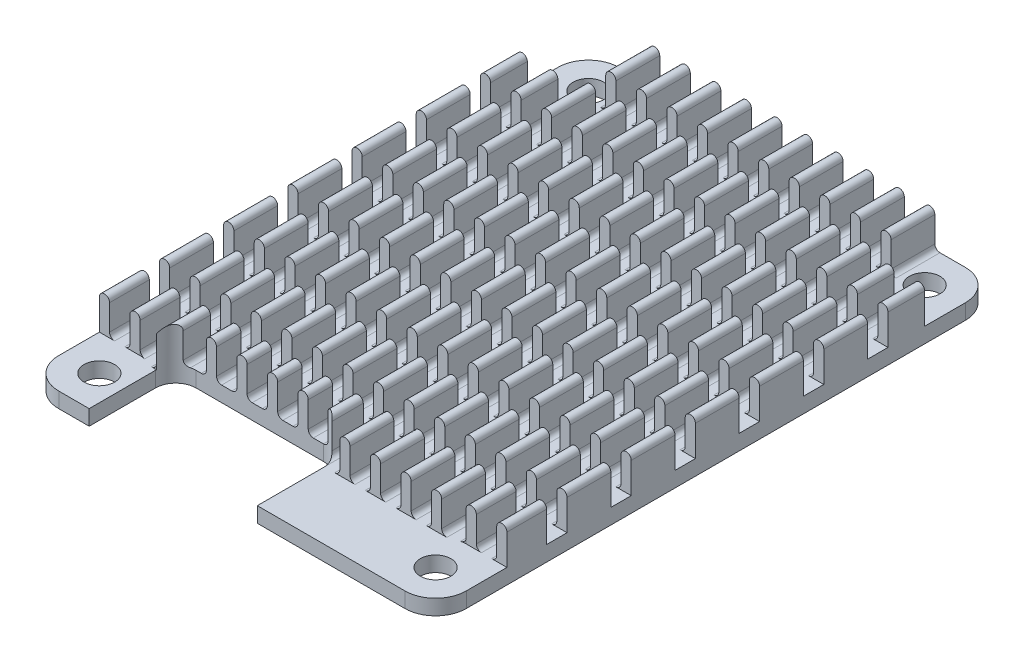
SolidWorks part; units mm, degrees
ref_plane "Ebene vorne" through (0, 0, 0) normal (0, 0, 1) x (1, 0, 0)
ref_plane "Ebene oben" through (0, 0, 0) normal (0, 1, 0) x (1, 0, 0)
ref_plane "Ebene rechts" through (0, 0, 0) normal (1, 0, 0) x (0, 0, -1)
sketch "Skizze1" plane through (0, 0, 0) normal (0, 1, 0) x (1, 0, 0)
  line L0 (20, -24.4903) -> (20, 24.4969)
  line L1 (17, 27.4969) -> (-17, 27.4969)
  line L2 (-20, 24.4969) -> (-20, -24.5035)
  line L3 (2.5, -27.5031) -> (17, -27.5031)
  line L4 (-20, -19.0031) -> (-20, -24.5035)
  line L5 (-16.9542, -27.5031) -> (-14, -27.5031)
  line L6 (-14, -27.5031) -> (-14, -21.0031)
  line L7 (-12.0085, -19.0031) -> (0.5, -19.0031)
  line L8 (2.5, -21.0077) -> (2.5, -27.5031)
  line L9 (2.5, -27.5031) -> (17, -27.5031)
  line L10 (20, -24.4903) -> (20, -19.0031)
  line L11 (-14, -27.5031) -> (-16.9542, -27.5031)
  line L13 (-25.9616, 32.7845) -> (24.6892, 32.7845)
  line L14 (-25.9616, 32.7845) -> (-25.9616, -32.0927)
  line L15 (-25.9616, -32.0927) -> (24.6892, -32.0927)
  line L16 (24.6892, 32.7845) -> (24.6892, -32.0927)
  circle A0 centre (-16.5, 23.9969) radius 1.5
  circle A1 centre (16.5, 23.9969) radius 1.5
  circle A2 centre (16.5, -24.0031) radius 1.5
  circle A3 centre (-16.5, -24.0031) radius 1.5
  arc A4 (20, 24.4969) -> (17, 27.4969) centre (17, 24.4969) ccw
  arc A5 (-17, 27.4969) -> (-20, 24.4969) centre (-17, 24.4969) ccw
  arc A6 (-20, -24.5035) -> (-16.9542, -27.5031) centre (-17, -24.5035) ccw
  arc A7 (-12.0085, -19.0031) -> (-14, -21.0031) centre (-12, -21.0031) ccw
  arc A8 (2.5, -21.0077) -> (0.5, -19.0031) centre (0.5, -21.0031) ccw
  arc A9 (17, -27.5031) -> (20, -24.4903) centre (17, -24.5031) ccw
  point P33 (0, 0)
extrude "Aufsatz-Linear austragen1" add sketch "Skizze1" along normal blind 1.5 contours L3 A9 L0 A4 L1 A5 L2 A6 L5 L6 A7 L7 A8 L8 A0 A1 A2 A3 region at (0.3933, 0, -1.5903)
sketch "Skizze2" plane through (0, 0, 0) normal (0, 0, 1) x (1, 0, 0)
  line L0 (-17, 0) -> (-16, 0)
  line L1 (-20, 0) -> (-19, 0)
  line L2 (-20, 0) -> (-20, 4.5)
  line L4 (-19, 0) -> (-19, 4.5)
  line L5 (-17, 0) -> (-17, 4.5)
  line L6 (-16, 0) -> (-16, 4.5)
  line L7 (-14, 0) -> (-13, 0)
  line L8 (-14, 0) -> (-14, 4.5)
  line L9 (-13, 0) -> (-13, 4.5)
  line L10 (-11, 0) -> (-10, 0)
  line L11 (-11, 0) -> (-11, 4.5)
  line L12 (-10, 0) -> (-10, 4.5)
  line L13 (-8, 0) -> (-7, 0)
  line L14 (-8, 0) -> (-8, 4.5)
  line L15 (-7, 0) -> (-7, 4.5)
  line L16 (-5, 0) -> (-4, 0)
  line L17 (-5, 0) -> (-5, 4.5)
  line L18 (-4, 0) -> (-4, 4.5)
  line L19 (-2, 0) -> (-1, 0)
  line L20 (-2, 0) -> (-2, 4.5)
  line L21 (-1, 0) -> (-1, 4.5)
  line L22 (1, 0) -> (2, 0)
  line L23 (1, 0) -> (1, 4.5)
  line L24 (2, 0) -> (2, 4.5)
  line L25 (4, 0) -> (5, 0)
  line L26 (4, 0) -> (4, 4.5)
  line L27 (5, 0) -> (5, 4.5)
  line L28 (7, 0) -> (8, 0)
  line L29 (7, 0) -> (7, 4.5)
  line L30 (8, 0) -> (8, 4.5)
  line L31 (10, 0) -> (11, 0)
  line L32 (10, 0) -> (10, 4.5)
  line L33 (11, 0) -> (11, 4.5)
  line L34 (13, 0) -> (14, 0)
  line L35 (13, 0) -> (13, 4.5)
  line L36 (14, 0) -> (14, 4.5)
  line L37 (16, 0) -> (17, 0)
  line L38 (16, 0) -> (16, 4.5)
  line L39 (17, 0) -> (17, 4.5)
  line L40 (19, 0) -> (20, 0)
  line L41 (19, 0) -> (19, 4.5)
  line L42 (20, 0) -> (20, 4.5)
  arc A0 (-19, 4.5) -> (-20, 4.5) centre (-19.5, 4.5) ccw
  arc A1 (-16, 4.5) -> (-17, 4.5) centre (-16.5, 4.5) ccw
  arc A2 (-13, 4.5) -> (-14, 4.5) centre (-13.5, 4.5) ccw
  arc A3 (-10, 4.5) -> (-11, 4.5) centre (-10.5, 4.5) ccw
  arc A4 (-7, 4.5) -> (-8, 4.5) centre (-7.5, 4.5) ccw
  arc A5 (-4, 4.5) -> (-5, 4.5) centre (-4.5, 4.5) ccw
  arc A6 (-1, 4.5) -> (-2, 4.5) centre (-1.5, 4.5) ccw
  arc A7 (2, 4.5) -> (1, 4.5) centre (1.5, 4.5) ccw
  arc A8 (5, 4.5) -> (4, 4.5) centre (4.5, 4.5) ccw
  arc A9 (8, 4.5) -> (7, 4.5) centre (7.5, 4.5) ccw
  arc A10 (11, 4.5) -> (10, 4.5) centre (10.5, 4.5) ccw
  arc A11 (14, 4.5) -> (13, 4.5) centre (13.5, 4.5) ccw
  arc A12 (17, 4.5) -> (16, 4.5) centre (16.5, 4.5) ccw
  arc A13 (20, 4.5) -> (19, 4.5) centre (19.5, 4.5) ccw
  dimension "D1" = 14
extrude "Aufsatz-Linear austragen2" add sketch "Skizze2" along normal up to surface (27.5031 mm away) from surface up to face at (9.75, 0.75, 27.5031) starting at face at (0, 0.75, -27.4969)
fillet "Verrundung1" radius 0.5 34 edges at (16, 1.5, -26.454) (19, 1.5, 0.0031) (16, 1.5, 0.0031) (16, 1.5, 26.4602) (13, 1.5, 0.0031) (10, 1.5, 0.0031) (7, 1.5, 0.0031) (4, 1.5, 0.0031) (1, 1.5, -4.2151) (-2, 1.5, -4.2469) (-5, 1.5, -4.2469) (-8, 1.5, -4.2469) (-11, 1.5, -4.2469) (-14, 1.5, 0.0031) (17, 1.5, -26.454) (17, 1.5, 0.0031) (17, 1.5, 26.4602) (14, 1.5, 0.0031) (11, 1.5, 0.0031) (8, 1.5, 0.0031) (5, 1.5, 0.0031) (2, 1.5, -3.9083) (-1, 1.5, -4.2469) (-4, 1.5, -4.2469) (-7, 1.5, -4.2469) (-10, 1.5, -4.2469) (-13, 1.5, -4.1129) (-16, 1.5, 26.4602) (-16, 1.5, 0.0031) (-16, 1.5, -26.454) (-17, 1.5, -26.454) (-17, 1.5, 0.0031) (-17, 1.5, 26.4602) (-19, 1.5, 0.0033)
sketch "Skizze4" plane through (0, 1.5, 0) normal (0, 1, 0) x (1, 0, 0)
  line L0 (-20, 24.4969) -> (-20, 27.4969)
  line L1 (-20, -16.6031) -> (20, -16.6031)
  line L2 (20, -16.6031) -> (20, -14.6031)
  line L3 (20, -14.6031) -> (-20, -14.6031)
  line L4 (-20, -14.6031) -> (-20, -16.6031)
  line L5 (-20, -10.3031) -> (20, -10.3031)
  line L6 (20, -10.3031) -> (20, -8.3031)
  line L7 (20, -8.3031) -> (-20, -8.3031)
  line L8 (-20, -8.3031) -> (-20, -10.3031)
  line L9 (-20, -4.0031) -> (20, -4.0031)
  line L10 (20, -4.0031) -> (20, -2.0031)
  line L11 (20, -2.0031) -> (-20, -2.0031)
  line L12 (-20, -2.0031) -> (-20, -4.0031)
  line L13 (-20, 2.2969) -> (20, 2.2969)
  line L14 (20, 2.2969) -> (20, 4.2969)
  line L15 (20, 4.2969) -> (-20, 4.2969)
  line L16 (-20, 4.2969) -> (-20, 2.2969)
  line L17 (-20, 8.5969) -> (20, 8.5969)
  line L18 (20, 8.5969) -> (20, 10.5969)
  line L19 (20, 10.5969) -> (-20, 10.5969)
  line L20 (-20, 10.5969) -> (-20, 8.5969)
  line L21 (-20, 14.8969) -> (20, 14.8969)
  line L22 (20, 14.8969) -> (20, 16.8969)
  line L23 (20, 16.8969) -> (-20, 16.8969)
  line L24 (-20, 16.8969) -> (-20, 14.8969)
  line L25 (-20, 24.4969) -> (-20, 20.4969)
  line L26 (-14, 23.1969) -> (14, 23.1969)
  line L27 (-17, 27.4969) -> (-14, 27.4969)
  line L28 (14.4805, 21.1969) -> (14.4801, 21.1969)
  line L29 (-20, -20.5031) -> (-20, -24.5031)
  line L30 (-20, -20.5031) -> (-16, -20.5031)
  line L31 (20, -20.5031) -> (20, -24.5031)
  line L32 (-14.8, -20.9031) -> (14.8, -20.9031)
  line L35 (16, -20.5031) -> (20, -20.5031)
  line L36 (14, -27.5031) -> (17, -27.5031)
  line L37 (-17, -27.5031) -> (-14, -27.5031)
  line L39 (-14.4801, 21.1969) -> (14.4801, 21.1969)
  line L40 (20, 24.4969) -> (20, 20.4969)
  line L41 (-20, 20.4969) -> (-16, 20.4969)
  line L42 (-14, 27.4969) -> (-14, 23.1969)
  line L43 (17, 27.4969) -> (14, 27.4969)
  line L44 (16, 20.4969) -> (20, 20.4969)
  line L45 (14, 27.4969) -> (14, 23.1969)
  line L46 (-20, 27.4969) -> (-17, 27.4969)
  line L47 (20, 24.4969) -> (20, 27.4969)
  line L48 (20, 27.4969) -> (17, 27.4969)
  line L49 (-20, -24.5031) -> (-20, -27.5031)
  line L50 (-20, -27.5031) -> (-17, -27.5031)
  line L51 (-14, -27.5031) -> (14, -27.5031)
  line L52 (17, -27.5031) -> (20, -27.5031)
  line L53 (20, -27.5031) -> (20, -24.5031)
  arc A2 (-16, 20.4969) -> (-14.4801, 21.1969) centre (-16, 22.4969) ccw
  arc A3 (14.4801, 21.1969) -> (16, 20.4969) centre (16, 22.4969) ccw
  arc A4 (-14.8, -20.9031) -> (-16, -20.5031) centre (-16, -22.5031) ccw
  arc A5 (16, -20.5031) -> (14.8, -20.9031) centre (16, -22.5031) ccw
extrude "Schnitt-Linear austragen7" cut sketch "Skizze4" along normal through all contours A3 L44 L45 L26 L42 L41 A2 L39 | L21 L22 L23 L24 | L17 L18 L19 L20 | L16 L13 L14 L15 | L12 L9 L10 L11 | L8 L5 L6 L7 | L4 L1 L2 L3 | L36 L52 L53 L31 L35 A5 L32 A4 L30 L29 L49 L50 L37 L51 | A3 L44 L40 L47 L48 L43 L45 L26 L42 L27 L46 L0 L25 L41 A2 L39 region at (-19.5939, 1.5, -25.9969)
extrude "Schnitt-Linear austragen1" cut sketch "Skizze1<4>" along normal through all contours A3 | L16 L13 L14 L15 A9 L3 L8 A8 L7 A7 L6 L5 A6 L2 A5 L1 A4 L0 | A2 | A1 | A0 region at (-0.6362, 0, -31.9614) region at (-16.5, 0, -23.9969) region at (16.5, 0, -23.9969) region at (16.5, 0, 24.0031) region at (-16.5, 0, 24.0031)
sketch "Skizze1<4>" plane through (0, 0, 0) normal (0, 1, 0) x (1, 0, 0) same geometry as "Skizze1"
fillet "Verrundung2" radius 0.5 2 edges at (-14, 1.5, -25.3469) (14, 1.5, -25.3469)
